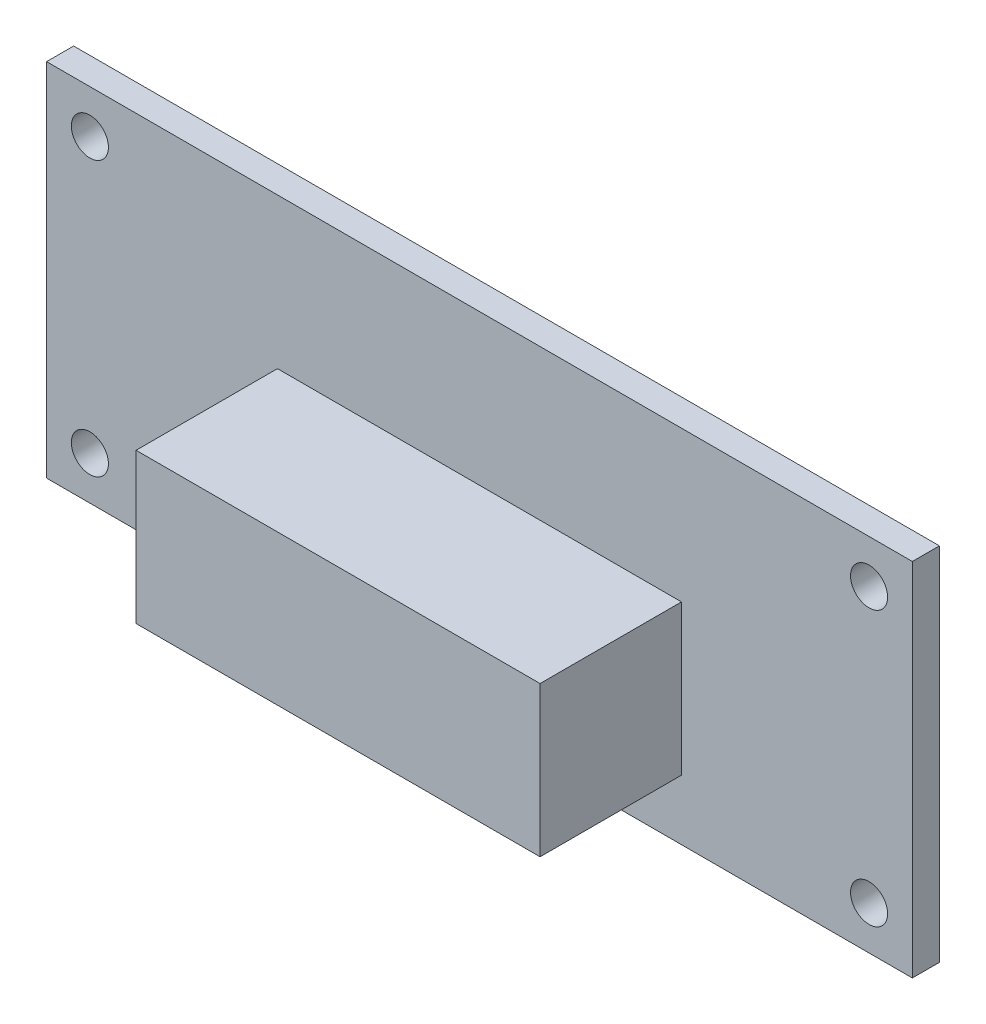
SolidWorks part; units mm, degrees
ref_plane "Front Plane" through (0, 0, 0) normal (0, 0, 1) x (1, 0, 0)
ref_plane "Top Plane" through (0, 0, 0) normal (0, 1, 0) x (1, 0, 0)
ref_plane "Right Plane" through (0, 0, 0) normal (1, 0, 0) x (0, 0, -1)
sketch "Sketch1" plane through (0, 0, 0) normal (0, 0, 1) x (1, 0, 0)
  line L1 (-38.1, -15.875) -> (38.1, -15.875)
  line L2 (-38.1, -15.875) -> (-38.1, 15.875)
  line L3 (-38.1, 15.875) -> (38.1, 15.875)
  line L4 (38.1, -15.875) -> (38.1, 15.875)
  line L5 (-38.1, -15.875) -> (38.1, 15.875) construction
  line L6 (-38.1, 15.875) -> (38.1, -15.875) construction
  point P0 (0, 0)
  dimension "D1" = 31.75
  dimension "D2" = 76.2
extrude "Boss-Extrude1" add sketch "Sketch1" along normal blind 2.3813
sketch "Sketch4" plane through (0, 0, 2.3813) normal (0, 0, 1) x (1, 0, 0)
  line L0 (-34.29, 15.875) -> (-34.29, 12.065) construction
  line L1 (38.1, 15.875) -> (-38.1, 15.875) construction
  line L2 (-34.29, 12.065) -> (-38.1, 12.065) construction
  line L3 (-38.1, 15.875) -> (-38.1, -15.875) construction
  dimension "D1" = 3.81
hole_wizard "#4 Clearance Hole1" positions "Sketch6" profile "Sketch5" hole size "#4" standard "ANSI Inch"
sketch "Sketch6" plane through (0, 0, 2.3813) normal (0, 0, 1) x (1, 0, 0)
  point P0 (-34.29, 12.065)
sketch "Sketch5" plane through (-34.29, 12.065, 2.3813) normal (1, 0, 0) x (0, -1, 0)
  line L0 (0, 0) -> (0, 4.1556)
  line L1 (0, 4.1556) -> (1.6319, 3.175)
  line L2 (1.6319, 3.175) -> (1.6319, 0)
  line L5 (1.6319, 0) -> (0, 0)
  line L10 (0, 4.1556) -> (-1.632, 3.175) construction
  line L11 (0, -6.35) -> (0, 107.95) construction
  dimension "Hole Dia." = 3.2639
  dimension "Hole Depth" = 3.175
  dimension "Drill Angle" = 118
mirror "Mirror1" about plane through (0, 0, 0) normal (1, 0, 0) of "#4 Clearance Hole1"
mirror "Mirror2" about plane through (0, 0, 0) normal (0, 1, 0) of "Mirror1"
sketch "Sketch2" plane through (0, 0, 2.3813) normal (0, 0, 1) x (1, 0, 0)
  line L1 (-17.78, -10.5745) -> (17.78, -10.5745)
  line L2 (-17.78, -10.5745) -> (-17.78, 2.6335)
  line L3 (-17.78, 2.6335) -> (17.78, 2.6335)
  line L4 (17.78, -10.5745) -> (17.78, 2.6335)
  line L5 (-17.78, -10.5745) -> (17.78, 2.6335) construction
  line L6 (-17.78, 2.6335) -> (17.78, -10.5745) construction
  point P0 (0, -3.9705)
  dimension "D1" = 35.56
  dimension "D2" = 13.208
extrude "Boss-Extrude2" add sketch "Sketch2" along normal blind 12.446
